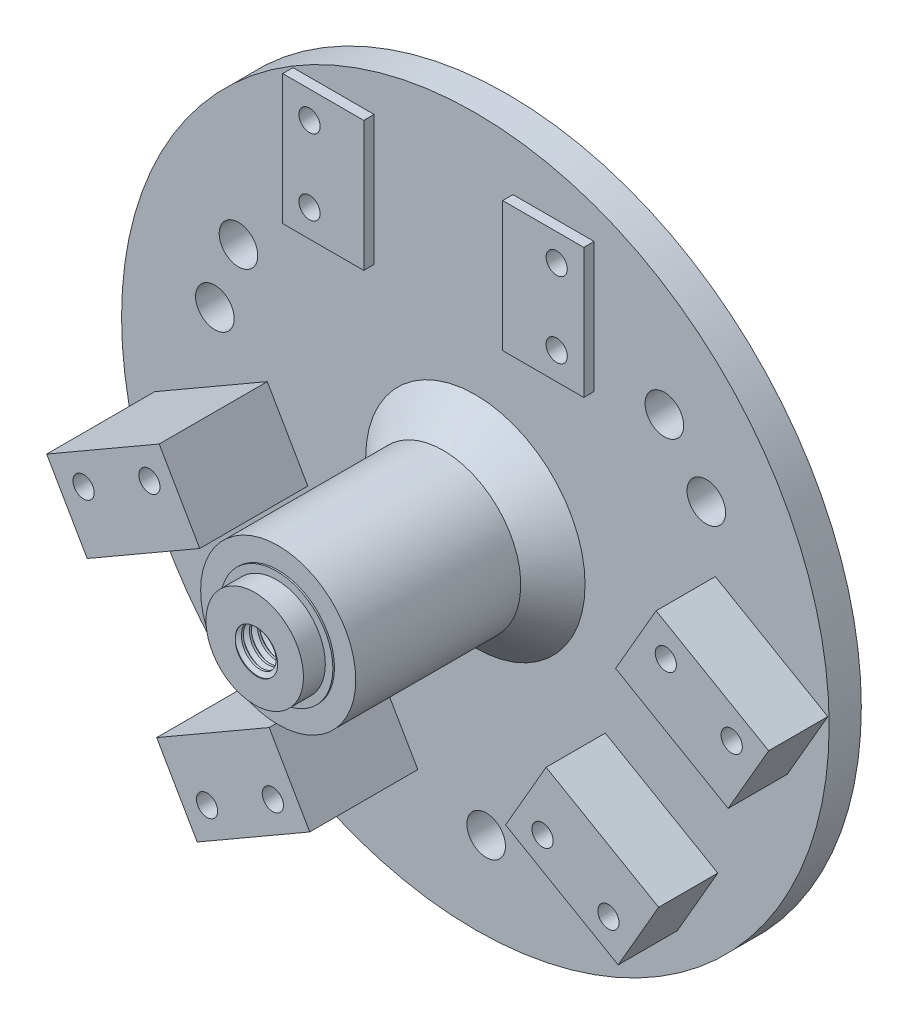
SolidWorks part; units mm, degrees
note: The reader was unsure of these and kept them because the rebuilt part matched: shared geometry of "Sketch4<4>", "Sketch4<5>", "Sketch5<4>", "Sketch5<5>", "Sketch11<3>", "Sketch11<4>".
ref_plane "Front Plane" through (0, 0, 0) normal (0, 0, 1) x (1, 0, 0)
ref_plane "Top Plane" through (0, 0, 0) normal (0, 1, 0) x (1, 0, 0)
ref_plane "Right Plane" through (0, 0, 0) normal (1, 0, 0) x (0, 0, -1)
other "Graphic1"
other "Graphic (Closed) -1"
sketch "Sketch3" plane through (0, 0, 0) normal (0, 1, 0) x (1, 0, 0)
  line L0 (-4.6454, -38.9) -> (-7.6454, -35.9)
  line L1 (0, 0) -> (-55, 0)
  line L2 (0, 0) -> (0, -5)
  line L3 (0, -5) -> (-55, -5)
  line L4 (-55, 0) -> (-55, -5)
  line L5 (0, -5) -> (-12.0548, -5)
  line L6 (0, -5) -> (0, -22.9)
  line L7 (0, -22.9) -> (-12.0548, -22.9)
  line L8 (-12.0548, -5) -> (-12.0548, -22.9)
  line L9 (-12.0548, -22.9) -> (-3.9654, -22.9)
  line L10 (-12.0548, -22.9) -> (-12.0548, -35.9)
  line L11 (-12.0548, -35.9) -> (-3.9654, -35.9)
  line L12 (-3.9654, -22.9) -> (-3.9654, -35.9)
  line L13 (-3.9654, -35.9) -> (-4.6454, -35.9)
  line L14 (-3.9654, -35.9) -> (-3.9654, -38.9)
  line L15 (-3.9654, -38.9) -> (-4.6454, -38.9)
  line L16 (-4.6454, -35.9) -> (-4.6454, -38.9)
  line L17 (-12.0548, -10) -> (-17.0548, -5)
  dimension "D1" = 12.0548
  dimension "D2" = 22.9
  dimension "D3" = 13
  dimension "D4" = 8.0893
  dimension "D5" = 3
  dimension "D6" = 0.68
  dimension "D7" = 45
  dimension "D8" = 45
  dimension "D9" = 5
  dimension "D10" = 55
revolve "Revolve1" add sketch "Sketch3" angle 360 about L6
sketch "Sketch2" plane through (0, 0, 5) normal (0, 0, 1) x (1, 0, 0)
  circle A2 centre (13.8035, -39.0138) radius 3
  circle A3 centre (35.8998, 20.5869) radius 3
  circle A4 centre (-40.4934, 8.5383) radius 3
  circle A5 centre (-36.8267, 18.8384) radius 3
  circle A6 centre (29.379, 29.0593) radius 3
  circle A7 centre (1.6765, -41.4173) radius 3
extrude "Cut-Extrude1" cut sketch "Sketch2" against normal blind 12 and the other way blind 10
sketch "Sketch4" plane through (0, 0, 5) normal (0, 0, 1) x (1, 0, 0)
  line L0 (20.1979, -18.4162) -> (37.6916, -28.5162)
  line L1 (37.6916, -28.5162) -> (31.3916, -39.4282)
  line L2 (31.3916, -39.4282) -> (13.8979, -29.3282)
  line L3 (13.8979, -29.3282) -> (20.1979, -18.4162)
  line L4 (37.2979, 11.2018) -> (30.9979, 0.2899)
  line L5 (30.9979, 0.2899) -> (48.4916, -9.8101)
  line L6 (48.4916, -9.8101) -> (54.7916, 1.1018)
  line L7 (54.7916, 1.1018) -> (37.2979, 11.2018)
  line L8 (18.45, 46.9) -> (18.45, 26.7)
  line L9 (18.45, 26.7) -> (5.85, 26.7)
  line L10 (5.85, 26.7) -> (5.85, 46.9)
  line L11 (5.85, 46.9) -> (18.45, 46.9)
  line L12 (-28.35, 46.9) -> (-15.75, 46.9)
  line L13 (-15.75, 46.9) -> (-15.75, 26.7)
  line L14 (-15.75, 26.7) -> (-28.35, 26.7)
  line L15 (-28.35, 26.7) -> (-28.35, 46.9)
  line L16 (-49.8416, -7.4718) -> (-32.3479, 2.6282)
  line L17 (-32.3479, 2.6282) -> (-26.0479, -8.2838)
  line L18 (-26.0479, -8.2838) -> (-43.5416, -18.3838)
  line L19 (-43.5416, -18.3838) -> (-49.8416, -7.4718)
  line L20 (-32.7416, -37.0899) -> (-15.2479, -26.9899)
  line L21 (-15.2479, -26.9899) -> (-8.9479, -37.9018)
  line L22 (-8.9479, -37.9018) -> (-26.4416, -48.0018)
  line L23 (-26.4416, -48.0018) -> (-32.7416, -37.0899)
extrude "Boss-Extrude1" add sketch "Sketch4" along normal blind 16.8 contours L19 L18 L17 L16 | L23 L22 L21 L20
extrude "Boss-Extrude2" add sketch "Sketch4<4>" along normal blind 1.6 contours L11 L10 L9 L8 | L15 L12 L13 L14
sketch "Sketch4<4>" plane through (0, 0, 5) normal (0, 0, 1) x (1, 0, 0) same geometry as "Sketch4"
extrude "Boss-Extrude3" add sketch "Sketch4<5>" along normal blind 9.2 contours L6 L7 L4 L5 | L2 L3 L0 L1
sketch "Sketch4<5>" plane through (0, 0, 5) normal (0, 0, 1) x (1, 0, 0) same geometry as "Sketch4"
sketch "Sketch5" plane through (0, 0, 0) normal (0, 0, -1) x (-1, 0, 0)
  line L0 (-38.8078, 5.4627) -> (-19.6459, -27.794)
  line L1 (-19.6459, -27.794) -> (-29.8856, -33.6939)
  line L2 (-29.8856, -33.6939) -> (-49.0475, -0.4372)
  line L3 (-49.0475, -0.4372) -> (-38.8078, 5.4627)
  line L4 (-14.2406, 42.6845) -> (24.1838, 42.6845)
  line L5 (24.1838, 42.6845) -> (24.1838, 30.9502)
  line L6 (24.1838, 30.9502) -> (-14.2406, 30.9502)
  line L7 (-14.2406, 30.9502) -> (-14.2406, 42.6845)
  line L8 (33.8758, -3.0998) -> (44.1, -8.9958)
  line L9 (44.1, -8.9958) -> (24.9082, -42.2761)
  line L10 (24.9082, -42.2761) -> (14.684, -36.3801)
  line L11 (14.684, -36.3801) -> (33.8758, -3.0998)
  circle A0 centre (33.8758, -3.0998) radius 3.1
  circle A1 centre (44.1, -8.9958) radius 3.1
  circle A2 centre (24.9082, -42.2761) radius 3.1
  circle A3 centre (14.684, -36.3801) radius 3.1
  circle A4 centre (-29.8856, -33.6939) radius 3.1
  circle A5 centre (-19.6459, -27.794) radius 3.1
  circle A6 centre (-49.0475, -0.4372) radius 3.1
  circle A7 centre (-38.8078, 5.4627) radius 3.1
  circle A8 centre (-14.2406, 30.9502) radius 3.1
  circle A9 centre (-14.2406, 42.6845) radius 3.1
  circle A10 centre (24.1838, 42.6845) radius 3.1
  circle A11 centre (24.1838, 30.9502) radius 3.1
  dimension "D1" = 6.2
  dimension "D2" = 38.4175
  dimension "D3" = 11.8024
extrude "Cut-Extrude5" cut sketch "Sketch5" against normal blind 4 contours L7 A8 L6 | L5 A10 L4 | L4 A10 L5 | A9 | A11
extrude "Cut-Extrude6" cut sketch "Sketch5<4>" against normal blind 18 contours A1 | A0 | A3 | A2
sketch "Sketch5<4>" plane through (0, 0, 0) normal (0, 0, -1) x (-1, 0, 0) same geometry as "Sketch5"
extrude "Cut-Extrude8" cut sketch "Sketch5<5>" against normal blind 10.4 contours A5 | A4 | A6 | A7
sketch "Sketch5<5>" plane through (0, 0, 0) normal (0, 0, -1) x (-1, 0, 0) same geometry as "Sketch5"
sketch "Sketch7" plane through (0, 0, 0) normal (0, 0, -1) x (-1, 0, 0)
  circle A0 centre (-38.8078, 5.4627) radius 1.65
  circle A1 centre (-38.8078, 5.4627) radius 3.1 construction
  circle A2 centre (-49.0475, -0.4372) radius 1.65
  circle A3 centre (-14.2406, 42.6845) radius 1.65
  circle A4 centre (-14.2406, 30.9502) radius 1.65
  circle A5 centre (24.1838, 30.9502) radius 1.65
  circle A6 centre (24.1838, 42.6845) radius 1.65
  circle A7 centre (44.1, -8.9958) radius 1.65
  circle A8 centre (33.8758, -3.0998) radius 1.65
  circle A9 centre (14.684, -36.3801) radius 1.65
  circle A10 centre (24.9082, -42.2761) radius 1.65
  circle A11 centre (-19.6459, -27.794) radius 1.65
  circle A12 centre (-29.8856, -33.6939) radius 1.65
  circle A14 centre (-19.6459, -27.794) radius 3.1 construction
  circle A15 centre (-29.8856, -33.6939) radius 3.1 construction
  dimension "D1" = 3.3
extrude "Cut-Extrude9" cut sketch "Sketch7" against normal through all contours A0
sketch "Sketch8" plane through (0, 0, 35.9) normal (0, 0, 1) x (1, 0, 0)
  line L0 (0, 0) -> (0, 12.0548)
  circle A0 centre (0, 0) radius 12.0548 construction
ref_plane "Plane1" through (0, 12.0548, 35.9) normal (0, 1, 0) x (1, 0, 0)
sketch "Sketch10" plane through (0, 12.0548, 35.9) normal (0, 1, 0) x (1, 0, 0)
  circle A0 centre (0, 7.988) radius 1
  dimension "D1" = 2
extrude "Cut-Extrude10" [suppressed] cut sketch "Sketch10" against normal through all
scale "Scale1" bodies to scale 111 scale about centroid uniform scaling yes scale factor 2
sketch "Sketch11" plane through (0, 0, 64.3027) normal (0, 0, 1) x (1, 0, 0)
  circle A0 centre (1.0125, 2.512) radius 15.15
  circle A1 centre (1.0125, 2.512) radius 24.1095 construction
  circle A2 centre (1.0125, 2.512) radius 24.1095
  circle A3 centre (1.0125, 2.512) radius 7.9308 construction
  circle A4 centre (1.0125, 2.512) radius 7.9308
  circle A5 centre (1.0125, 2.512) radius 17.5
  dimension "D1" = 30.3
  dimension "D2" = 35
extrude "Cut-Extrude11" cut sketch "Sketch11" along normal through all contours A2
extrude "Boss-Extrude4" add sketch "Sketch11<3>" along normal blind 6.8 contours A0 A4
sketch "Sketch11<3>" plane through (0, 0, 64.3027) normal (0, 0, 1) x (1, 0, 0) same geometry as "Sketch11"
extrude "Cut-Extrude12" cut sketch "Sketch11<4>" against normal blind 0.5 contours A2 | A5
sketch "Sketch11<4>" plane through (0, 0, 64.3027) normal (0, 0, 1) x (1, 0, 0) same geometry as "Sketch11"
sketch "Sketch18" plane through (0, 0, 71.1027) normal (0, 0, 1) x (1, 0, 0)
  circle A0 centre (1.0125, 2.512) radius 6
  circle M1 centre (1.0125, 2.512) radius 7.9308
  dimension "D1" = 12
extrude "Boss-Extrude6" add sketch "Sketch18" against normal up to surface (32.8 mm away) contours A0 M1
thread "Thread1" pitch 2.5 start angle 0, offset 5, length 0, pitch 2.5, diameter 12
ref_plane "Plane2" through (-4.9875, 2.512, 76.1027) normal (0, -1, 0) x (-1, 0, 0)
sketch "Thread Profile1" plane through (-4.9875, 2.512, 76.1027) normal (0, -1, 0) x (-1, 0, 0)
  line L0 (0, 0) -> (0, 2.5) construction
  line L1 (0, 0) -> (1.3532, 0.7812)
  line L2 (1.3532, 0.7812) -> (1.3532, 1.0937)
  line L3 (1.3532, 1.0937) -> (0, 1.875)
  line L4 (1.3532, 0.9375) -> (0, 0.9375) construction
  line L11 (0, 0) -> (0, 1.875)
  point P2 (0, 0)
  dimension "Pitch" = 2.5
  dimension "Profile_Angle" = 60
  dimension "Profile_Land" = 0.3125
  dimension "Profile_Height" = 1.3532
sketch "Sketch17" plane through (0, 0, 38.3027) normal (0, 0, 1) x (1, 0, 0)
  circle A0 centre (1.0125, 2.512) radius 24.1095 construction
  circle A1 centre (1.0125, 2.512) radius 24.1095
extrude "Boss-Extrude5" add sketch "Sketch17" against normal up to surface (35.8 mm away)
